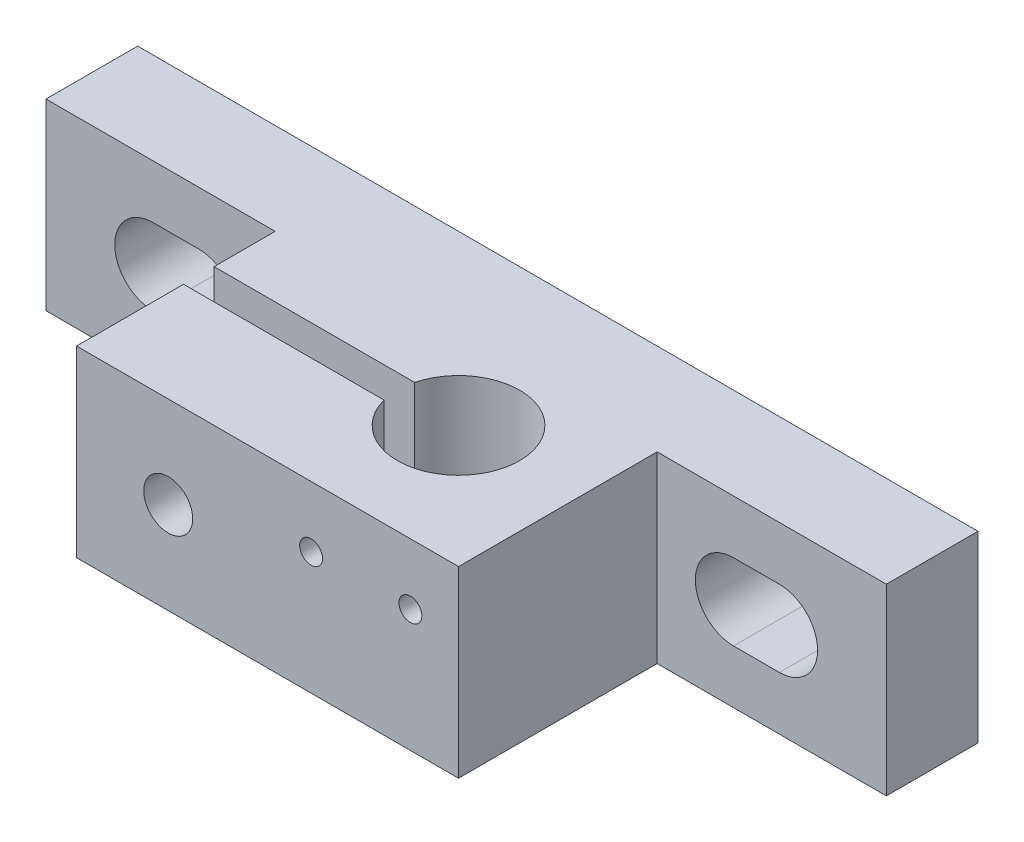
SolidWorks part; units mm, degrees
material "Copper"
ref_plane "Front Plane" through (0, 0, 0) normal (0, 0, 1) x (1, 0, 0)
ref_plane "Top Plane" through (0, 0, 0) normal (0, 1, 0) x (1, 0, 0)
ref_plane "Right Plane" through (0, 0, 0) normal (1, 0, 0) x (0, 0, -1)
sketch "Sketch2" plane through (0, 0, 0) normal (0, 0, 1) x (1, 0, 0)
  line L0 (7, 6) -> (10, 6) construction
  line L1 (0, 0) -> (55, 0)
  line L2 (0, 0) -> (0, 12)
  line L3 (0, 12) -> (55, 12)
  line L4 (55, 0) -> (55, 12)
  line L5 (27.5, 12) -> (27.5, -3.75) construction
  line L6 (7, 8.5) -> (10, 8.5)
  line L7 (7, 3.5) -> (10, 3.5)
  line L8 (48, 6) -> (45, 6) construction
  line L9 (48, 8.5) -> (45, 8.5)
  line L10 (48, 3.5) -> (45, 3.5)
  arc A0 (7, 8.5) -> (7, 3.5) centre (7, 6) ccw
  arc A1 (48, 8.5) -> (48, 3.5) centre (48, 6) cw
  arc A2 (10, 3.5) -> (10, 8.5) centre (10, 6) ccw
  arc A3 (45, 3.5) -> (45, 8.5) centre (45, 6) cw
  point P11 (8.5, 6)
  point P16 (46.5, 6)
  dimension "D1" = 7
  dimension "D2" = 3
  dimension "D5" = 55
extrude "Boss-Extrude1" add sketch "Sketch2" along normal blind 6
sketch "Sketch3" plane through (0, 0, 6) normal (0, 0, 1) x (1, 0, 0)
  line L0 (0, 0) -> (55, 0) construction
  line L1 (15, 0) -> (40, 0)
  line L2 (15, 0) -> (15, 12)
  line L3 (15, 12) -> (40, 12)
  line L4 (40, 0) -> (40, 12)
  line L5 (55, 12) -> (0, 12) construction
  line L6 (0, 12) -> (0, 0) construction
  line L7 (55, 0) -> (55, 12) construction
  dimension "D1" = 25
  dimension "D2" = 15
  dimension "D3" = 15
extrude "Boss-Extrude2" add sketch "Sketch3" along normal blind 13
sketch "Sketch4" plane through (0, 0, 0) normal (0, -1, 0) x (1, 0, 0)
  line L0 (15, 19) -> (40, 19) construction
  line L1 (40, 19) -> (40, 6) construction
  line L2 (0, 0) -> (55, 0) construction
  line L3 (28.127, 12) -> (15, 12)
  line L4 (15, 19) -> (15, 6) construction
  line L5 (15, 12) -> (15, 10)
  line L6 (15, 10) -> (28.127, 10)
  circle A0 centre (32, 11) radius 4
  line M4 (15, 19) -> (15, 6)
  dimension "D1" = 8
  dimension "D5" = 8
  dimension "D7" = 11
  dimension "D2" = 8
  dimension "D3" = 11
  dimension "D4" = 1
  dimension "D6" = 1
extrude "Cut-Extrude2" cut sketch "Sketch4" against normal blind 30 contours A0 L3 L6 M4 | A0 region at (21.5211, 0, 11) region at (32, 0, 11)
sketch "Sketch5" plane through (0, 0, 0) normal (0, 0, -1) x (-1, 0, 0)
  line L0 (-55, 12) -> (0, 12) construction
  line L1 (-37.6724, 9.5) -> (-17.1585, 9.5)
  line L2 (-37.6724, 9.5) -> (-37.6724, 2.5)
  line L3 (-37.6724, 2.5) -> (-17.1585, 2.5)
  line L4 (-17.1585, 9.5) -> (-17.1585, 2.5)
  line L5 (0, 0) -> (-55, 0) construction
  line L6 (0, 12) -> (0, 0) construction
  dimension "D1" = 20.5139
  dimension "D2" = 2.5
  dimension "D3" = 2.5
  dimension "D4" = 17.1585
extrude "Cut-Extrude3" cut sketch "Sketch5" against normal blind 5
sketch "Sketch6" plane through (0, 0, 19) normal (0, 0, 1) x (1, 0, 0)
  line L0 (15, 12) -> (15, 0) construction
  line L1 (40, 12) -> (15, 12) construction
  line L2 (15, 0) -> (40, 0) construction
  circle A0 centre (21, 6) radius 1.6
  dimension "D1" = 6
  dimension "D2" = 6
  dimension "D3" = 6
extrude "Cut-Extrude4" cut sketch "Sketch6" against normal blind 20
sketch "Sketch7" plane through (0, 0, 5) normal (0, 0, -1) x (-1, 0, 0)
  line L1 (-17.5359, 6) -> (-19.2679, 9)
  line L2 (-19.2679, 9) -> (-22.7321, 9)
  line L3 (-22.7321, 9) -> (-24.4641, 6)
  line L4 (-24.4641, 6) -> (-22.7321, 3)
  line L5 (-22.7321, 3) -> (-19.2679, 3)
  line L6 (-19.2679, 3) -> (-17.5359, 6)
  circle A0 centre (-21, 6) radius 3 construction
extrude "Cut-Extrude5" cut sketch "Sketch7" against normal blind 3
sketch "Sketch8" plane through (0, 0, 19) normal (0, 0, 1) x (1, 0, 0)
  line L0 (40, 0) -> (40, 12) construction
  line L1 (40, 12) -> (15, 12) construction
  circle A0 centre (36.85, 8) radius 0.75
  circle A1 centre (30.35, 8) radius 0.75
  dimension "D1" = 1.5
  dimension "D2" = 3.15
  dimension "D3" = 4
  dimension "D4" = 2
extrude "Cut-Extrude6" cut sketch "Sketch8" against normal blind 3
